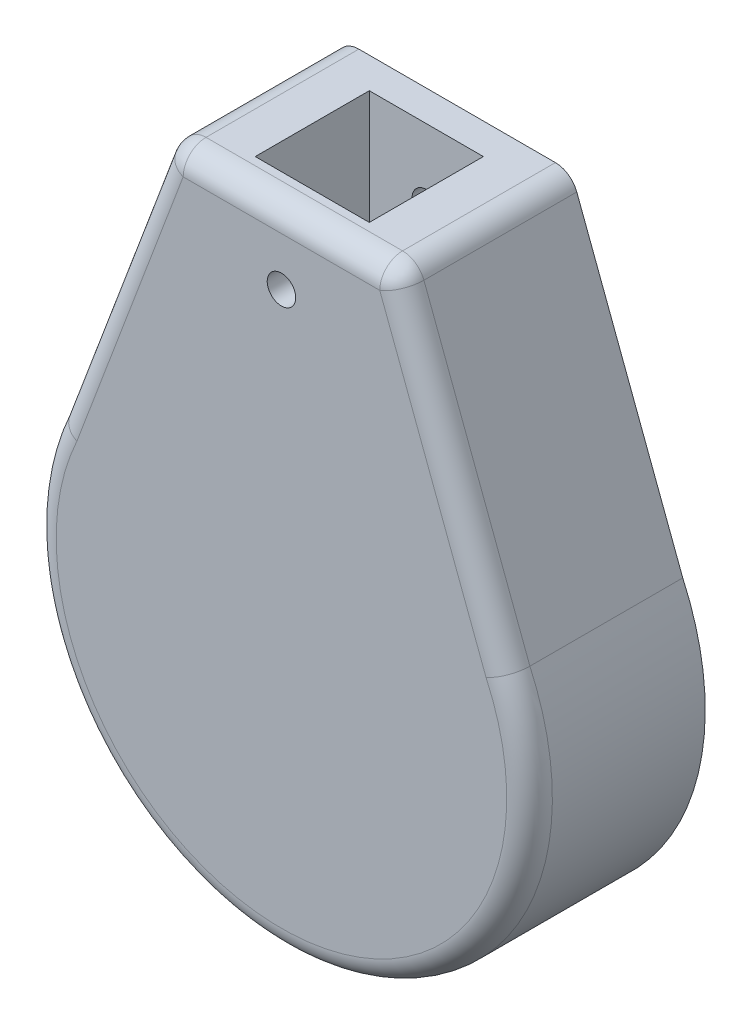
SolidWorks part; units mm, degrees
ref_plane "Alzado" through (0, 0, 0) normal (0, 0, 1) x (1, 0, 0)
ref_plane "Planta" through (0, 0, 0) normal (0, 1, 0) x (1, 0, 0)
ref_plane "Vista lateral" through (0, 0, 0) normal (1, 0, 0) x (0, 0, -1)
sketch "Croquis1" plane through (0, 0, 0) normal (0, 0, 1) x (1, 0, 0)
  line L0 (-43.5, 0) -> (43.5, 0) construction
  line L1 (0, 43.5) -> (0, -43.5) construction
  line L2 (0, 0) -> (-30.7591, 30.7591) construction
  line L3 (0, 0) -> (26.6453, -26.6453) construction
  line L4 (30.7591, 30.7591) -> (0, 0) construction
  line L5 (0, 0) -> (-30.7591, -30.7591) construction
  line L6 (-2.4, 33.5142) -> (-2.4, 35.4188)
  line L7 (2.4, 33.5142) -> (2.4, 35.4188)
  line L8 (2.4, -33.5142) -> (2.4, -35.4188)
  line L9 (-2.4, -33.5142) -> (-2.4, -35.4188)
  line L10 (-35.4188, 2.4) -> (-33.5142, 2.4)
  line L11 (-35.4188, -2.4) -> (-33.5142, -2.4)
  line L12 (35.4188, -2.4) -> (33.5142, -2.4)
  line L13 (35.4188, 2.4) -> (33.5142, 2.4)
  line L14 (-23.3478, 26.7419) -> (-22.001, 25.3952)
  line L15 (-26.7419, 23.3478) -> (-25.3952, 22.001)
  line L16 (26.7419, -23.3478) -> (25.3952, -22.001)
  line L17 (23.3478, -26.7419) -> (22.001, -25.3952)
  line L18 (22.001, 25.3952) -> (23.3478, 26.7419)
  line L19 (25.3952, 22.001) -> (26.7419, 23.3478)
  line L20 (-22.001, -25.3952) -> (-23.3478, -26.7419)
  line L21 (-25.3952, -22.001) -> (-26.7419, -23.3478)
  circle A0 centre (0, 0) radius 43.5
  arc A1 (-23.3478, 26.7419) -> (-26.7419, 23.3478) centre (0, 0) ccw
  arc A2 (-2.4, 33.5142) -> (-22.001, 25.3952) centre (0, 0) ccw
  arc A3 (2.4, 35.4188) -> (-2.4, 35.4188) centre (0, 0) ccw
  arc A4 (-25.3952, 22.001) -> (-33.5142, 2.4) centre (0, 0) ccw
  arc A5 (22.001, 25.3952) -> (2.4, 33.5142) centre (0, 0) ccw
  arc A6 (26.7419, 23.3478) -> (23.3478, 26.7419) centre (0, 0) ccw
  arc A7 (33.5142, 2.4) -> (25.3952, 22.001) centre (0, 0) ccw
  arc A8 (35.4188, -2.4) -> (35.4188, 2.4) centre (0, 0) ccw
  arc A9 (25.3952, -22.001) -> (33.5142, -2.4) centre (0, 0) ccw
  arc A10 (23.3478, -26.7419) -> (26.7419, -23.3478) centre (0, 0) ccw
  arc A11 (2.4, -33.5142) -> (22.001, -25.3952) centre (0, 0) ccw
  arc A12 (-2.4, -35.4188) -> (2.4, -35.4188) centre (0, 0) ccw
  arc A13 (-22.001, -25.3952) -> (-2.4, -33.5142) centre (0, 0) ccw
  arc A14 (-26.7419, -23.3478) -> (-23.3478, -26.7419) centre (0, 0) ccw
  arc A15 (-33.5142, -2.4) -> (-25.3952, -22.001) centre (0, 0) ccw
  arc A16 (-35.4188, 2.4) -> (-35.4188, -2.4) centre (0, 0) ccw
  dimension "D1" = 87
  dimension "D2" = 71
  dimension "D6" = 67.2
  dimension "D3" = 45
  dimension "D4" = 45
  dimension "D5" = 45
  dimension "D7" = 2.4
  dimension "D8" = 2.4
  dimension "D9" = 2.4
  dimension "D10" = 2.4
  dimension "D11" = 2.4
  dimension "D12" = 2.4
  dimension "D13" = 2.4
  dimension "D14" = 2.4
extrude "Saliente-Extruir4" add sketch "Croquis1" along normal blind 12.8 contours A0 | L14 A2 L6 A3 L7 A5 L18 A6 L19 A7 L13 A8 L12 A9 L16 A10 L17 A11 L8 A12 L9 A13 L20 A14 L21 A15 L11 A16 L10 A4 L15 A1
sketch "Croquis2" plane through (0, 0, 12.8) normal (0, 0, 1) x (1, 0, 0)
  line L0 (0, 0) -> (0, 115.8162) construction
  circle A0 centre (0, 0) radius 43.5
  dimension "D1" = 87
extrude "Saliente-Extruir5" add sketch "Croquis2" along normal blind 18
sketch "Croquis3" plane through (0, 0, 0) normal (0, 0, 1) x (1, 0, 0)
  line L0 (-43.5, 0) -> (43.5, 0) construction
  line L1 (43.5, 0) -> (20, 70) construction
  line L2 (20, 70) -> (-20, 70) construction
  line L3 (-20, 70) -> (-43.5, 0) construction
  line L4 (0, 0) -> (0, 70) construction
  line L5 (-20, 70) -> (-39.5567, 18.0975)
  line L6 (20, 70) -> (39.5567, 18.0975)
  line L7 (-20, 70) -> (20, 70)
  circle A0 centre (0, 0) radius 43.5 construction
  circle A2 centre (0, 0) radius 43.5
  arc A3 (39.5567, 18.0975) -> (-39.5567, 18.0975) centre (0, 0) ccw
  dimension "D1" = 70
  dimension "D2" = 40
  dimension "D3" = 20
  dimension "D4" = 51.9025
  dimension "D5" = 55.4647
  dimension "D6" = 0
extrude "Saliente-Extruir6" add sketch "Croquis3" along normal through all
sketch "Croquis4" plane through (0, 70, 0) normal (0, 1, 0) x (1, 0, 0)
  line L0 (0, 0) -> (0, -30.8) construction
  line L1 (20, -30.8) -> (-20, -30.8) construction
  line L2 (-20, -15.4) -> (20, -15.4) construction
  line L3 (-20, -30.8) -> (-20, 0) construction
  line L4 (20, -30.8) -> (20, 0) construction
  line L6 (-10, -5.4) -> (10, -5.4)
  line L7 (-10, -5.4) -> (-10, -25.4)
  line L8 (-10, -25.4) -> (10, -25.4)
  line L9 (10, -5.4) -> (10, -25.4)
  line L10 (-10, -5.4) -> (10, -25.4) construction
  line L11 (-10, -25.4) -> (10, -5.4) construction
  point P11 (0, -15.4)
  dimension "D1" = 20
  dimension "D2" = 20
extrude "Cortar-Extruir1" cut sketch "Croquis4" against normal blind 25
sketch "Croquis5" plane through (0, 0, 0) normal (0, 0, -1) x (-1, 0, 0)
  line L0 (0, 0) -> (0, 70) construction
  line L1 (-20, 70) -> (20, 70) construction
  circle A0 centre (0, 57.5) radius 2.5
  dimension "D1" = 5
  dimension "D2" = 12.5
extrude "Cortar-Extruir2" cut sketch "Croquis5" against normal blind 42
fillet "Redondeo1" radius 4 3 edges at (0, -43.5, 30.8) (-29.7783, 44.0487, 30.8) (29.7783, 44.0487, 30.8)
fillet "Redondeo2" radius 4 5 edges at (20, 70, 13.4) (18.748, 70, 29.6284) (0, 70, 30.8) (-18.748, 70, 29.6284) (-20, 70, 13.4)
